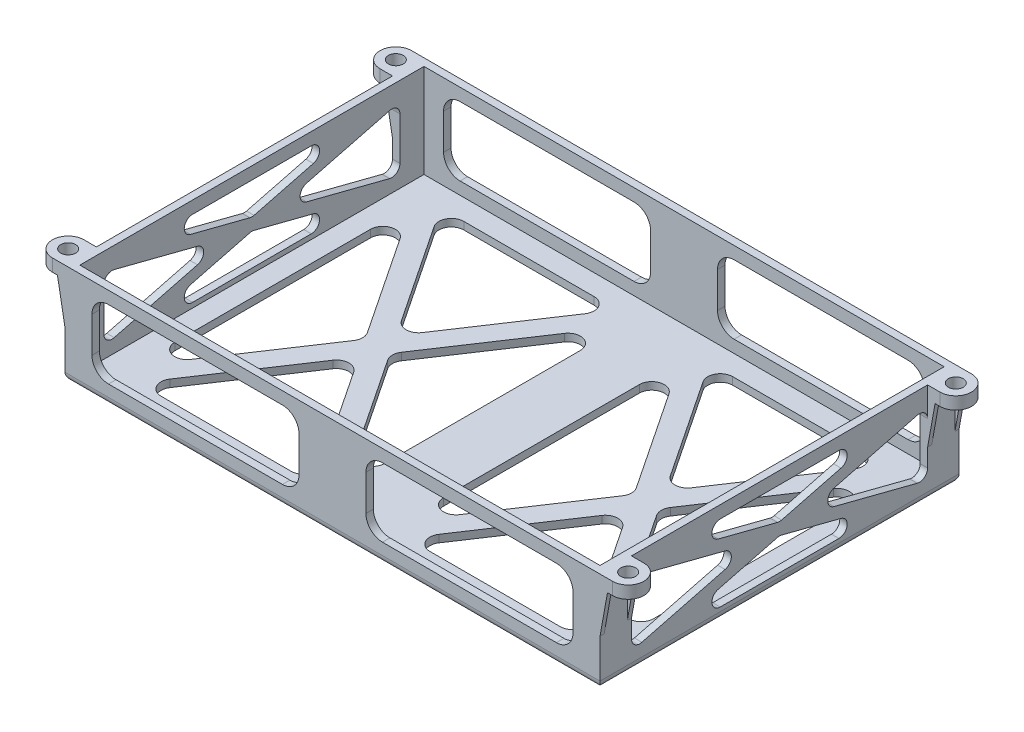
SolidWorks part; units mm, degrees
other "Markup2"
sketch "Sketch32" plane through (-159.4724, 0, 108) normal (-0.262, -0.0774, 0.962) x (0.8638, -0.4632, 0.198)
ref_plane "Front Plane" through (0, 0, 0) normal (0, 0, 1) x (1, 0, 0)
ref_plane "Top Plane" through (0, 0, 0) normal (0, 1, 0) x (1, 0, 0)
ref_plane "Right Plane" through (0, 0, 0) normal (1, 0, 0) x (0, 0, -1)
sketch "Sketch1" plane through (0, 0, 0) normal (0, 1, 0) x (1, 0, 0)
  line L0 (-2.286, -2.286) -> (-2.286, -107.823) construction
  line L1 (0, 0) -> (-164.084, 0)
  line L2 (0, 0) -> (0, -110.109)
  line L3 (0, -110.109) -> (-164.084, -110.109)
  line L4 (-164.084, 0) -> (-164.084, -110.109)
  line L5 (-2.286, -107.823) -> (-161.798, -107.823) construction
  line L6 (-161.798, -2.286) -> (-161.798, -107.823) construction
  line L7 (-2.286, -2.286) -> (-161.798, -2.286) construction
  dimension "D1" = 2.286
  dimension "D2" = 105.537
  dimension "D3" = 159.512
extrude "Boss-Extrude1" add sketch "Sketch1" along normal blind 30.988 contours L1 L4 L3 L2
shell "Shell1" thickness 2.286 removed face at (-82.042, 30.988, 55.0545)
sketch "Sketch7" plane through (0, 30.988, 0) normal (0, 1, 0) x (1, 0, 0)
  line L0 (-167.894, 0) -> (-164.084, 0)
  line L1 (-164.084, 0) -> (-164.084, -9.652)
  line L2 (-164.084, 0) -> (-164.084, -110.109) construction
  line L3 (-164.084, -9.652) -> (-167.894, -9.652)
  line L4 (-82.042, -1000) -> (-82.042, 49000) construction
  line L5 (0, 0) -> (-164.084, 0) construction
  line L6 (-1150, -55.0545) -> (48850, -55.0545) construction
  line L7 (-161.798, -2.286) -> (-161.798, -107.823) construction
  line L8 (-164.084, -100.457) -> (-167.894, -100.457)
  line L9 (-164.084, -110.109) -> (-164.084, -100.457)
  line L10 (-167.894, -110.109) -> (-164.084, -110.109)
  line L11 (3.81, -110.109) -> (0, -110.109)
  line L12 (0, -110.109) -> (0, -100.457)
  line L13 (0, -100.457) -> (3.81, -100.457)
  line L14 (0, -9.652) -> (3.81, -9.652)
  line L15 (0, 0) -> (0, -9.652)
  line L16 (3.81, 0) -> (0, 0)
  circle A0 centre (-167.894, -4.826) radius 2.286
  arc A2 (-167.894, 0) -> (-167.894, -9.652) centre (-167.894, -4.826) ccw
  arc A3 (-167.894, -110.109) -> (-167.894, -100.457) centre (-167.894, -105.283) cw
  circle A4 centre (-167.894, -105.283) radius 2.286
  circle A5 centre (3.81, -105.283) radius 2.286
  arc A6 (3.81, -110.109) -> (3.81, -100.457) centre (3.81, -105.283) ccw
  arc A7 (3.81, 0) -> (3.81, -9.652) centre (3.81, -4.826) cw
  circle A8 centre (3.81, -4.826) radius 2.286
  point P14 (-82.042, 0)
  point P19 (-161.798, -55.0545)
  dimension "D1" = 2.54
  dimension "D3" = 4.572
  dimension "D2" = 3.81
extrude "Boss-Extrude7" add sketch "Sketch7" against normal blind 3.81
ref_plane "Plane1" through (0, 0, 55.0545) normal (0, 0, -1) x (-1, 0, 0)
ref_plane "Plane2" through (-82.042, 0, 0) normal (-1, 0, 0) x (0, 0, 1)
sketch "Sketch33" plane through (0, 0, 0) normal (1, 0, 0) x (0, 0, -1)
  line L0 (-9.652, 27.178) -> (-100.457, 3.81) construction
  line L1 (-9.652, 27.178) -> (-100.457, 27.178)
  line L2 (-9.652, 27.178) -> (-9.652, 3.81)
  line L3 (-9.652, 3.81) -> (-100.457, 3.81)
  line L4 (-100.457, 27.178) -> (-100.457, 3.81)
  line L5 (-9.652, 3.81) -> (-100.457, 27.178) construction
  line L6 (-9.652, 27.178) -> (-9.652, 30.988) construction
  line L7 (-55.0545, 17.3299) -> (-93.3228, 27.178)
  line L8 (-9.652, 30.988) -> (-100.457, 30.988) construction
  line L10 (0, 27.178) -> (-9.652, 27.178) construction
  line L11 (-55.0545, 13.6581) -> (-93.3228, 3.81)
  line L12 (0, 0) -> (-110.109, 0) construction
  line L13 (-9.652, 5.6459) -> (-47.9203, 15.494)
  line L14 (-16.7862, 27.178) -> (-55.0545, 17.3299)
  line L15 (-16.7862, 3.81) -> (-55.0545, 13.6581)
  line L16 (-9.652, 25.3421) -> (-47.9203, 15.494)
  line L17 (-9.2089, 25.4561) -> (-100.0139, 2.0881) construction
  line L18 (-10.0951, 28.8999) -> (-100.9001, 5.5319) construction
  line L19 (-9.2089, 5.5319) -> (-100.0139, 28.8999) construction
  line L20 (-10.0951, 2.0881) -> (-100.9001, 25.4561) construction
  line L21 (-62.1887, 15.494) -> (-100.457, 5.6459)
  line L22 (-62.1887, 15.494) -> (-100.457, 25.3421)
  point P10 (-55.0545, 30.988)
  point P12 (-55.0545, 27.178)
  dimension "D1" = 3.81
  dimension "D2" = 1.778
  dimension "D3" = 1.778
extrude "Cut-Extrude1" cut sketch "Sketch33" against normal up to surface (2.286 mm away) contours L3 L15 L11 | L2 L16 L13 | L21 L22 L4 | L14 L1 L7 region at (0, 23.8953, 55.0545) region at (0, 15.494, 22.4081) region at (0, 15.494, 87.7009) region at (0, 7.0927, 55.0545) up to face at (-2.286, 16.637, 55.0545)
fillet "Fillet1" radius 2.54 12 edges at (-1.143, 3.81, 16.7862) (-1.143, 13.6581, 55.0545) (-1.143, 3.81, 93.3228) (-1.143, 5.6459, 100.457) (-1.143, 25.3421, 100.457) (-1.143, 15.494, 62.1887) (-1.143, 17.3299, 55.0545) (-1.143, 27.178, 93.3228) (-1.143, 27.178, 16.7862) (-1.143, 5.6459, 9.652) (-1.143, 25.3421, 9.652) (-1.143, 15.494, 47.9203)
mirror "Mirror1" about plane through (-82.042, 0, 0) normal (-1, 0, 0) of "Fillet1", "Cut-Extrude1"
sketch "Sketch34" plane through (0, 0, 107.823) normal (0, 0, -1) x (-1, 0, 0)
  line L0 (92.298, 16.637) -> (71.786, 16.637) construction
  line L1 (150.718, 6.096) -> (97.378, 6.096)
  line L2 (155.798, 11.176) -> (155.798, 22.098)
  line L3 (150.718, 27.178) -> (97.378, 27.178)
  line L4 (92.298, 11.176) -> (92.298, 22.098)
  line L5 (66.706, 6.096) -> (13.366, 6.096)
  line L6 (71.786, 11.176) -> (71.786, 22.098)
  line L7 (66.706, 27.178) -> (13.366, 27.178)
  line L8 (8.286, 11.176) -> (8.286, 22.098)
  line L9 (2.286, 30.988) -> (161.798, 30.988) construction
  line L10 (161.798, 30.988) -> (161.798, 2.286) construction
  line L11 (2.286, 2.286) -> (161.798, 2.286) construction
  arc A0 (150.718, 6.096) -> (155.798, 11.176) centre (150.718, 11.176) ccw
  arc A1 (155.798, 22.098) -> (150.718, 27.178) centre (150.718, 22.098) ccw
  arc A2 (97.378, 27.178) -> (92.298, 22.098) centre (97.378, 22.098) ccw
  arc A3 (97.378, 6.096) -> (92.298, 11.176) centre (97.378, 11.176) cw
  arc A4 (13.366, 6.096) -> (8.286, 11.176) centre (13.366, 11.176) cw
  arc A5 (66.706, 6.096) -> (71.786, 11.176) centre (66.706, 11.176) ccw
  arc A6 (71.786, 22.098) -> (66.706, 27.178) centre (66.706, 22.098) ccw
  arc A7 (13.366, 27.178) -> (8.286, 22.098) centre (13.366, 22.098) ccw
  point P12 (82.042, 30.988)
  point P13 (82.042, 16.637)
  point P16 (161.798, 16.637)
  point P17 (155.798, 16.637)
  point P30 (8.286, 6.096)
  point P33 (71.786, 6.096)
  dimension "D4" = 5.08
  dimension "D1" = 6
  dimension "D2" = 63.5
  dimension "D3" = 3.81
extrude "Cut-Extrude2" cut sketch "Sketch34" against normal through all both and the other way through all
fillet "Fillet2" radius 2.54 4 edges at (-82.042, 0, 0) (-164.084, 0, 55.0545) (-82.042, 0, 110.109) (0, 0, 55.0545)
sketch "Sketch36" plane through (0, 2.286, 0) normal (0, 1, 0) x (1, 0, 0)
  line L0 (-103.2935, -8.636) -> (-143.2465, -8.636)
  line L2 (-164.084, 0) -> (-164.084, -110.109) construction
  line L4 (-151.638, -97.663) -> (-94.902, -12.446) construction
  line L6 (-91.092, -85.059) -> (-91.092, -25.05)
  line L7 (-151.638, -12.446) -> (-94.902, -97.663) construction
  line L9 (0, 0) -> (-164.084, 0) construction
  line L11 (-164.084, -110.109) -> (0, -110.109) construction
  line L14 (-155.448, -25.05) -> (-155.448, -85.059)
  line L15 (-143.2465, -101.473) -> (-103.2935, -101.473)
  line L16 (-155.6918, -103.7518) -> (-93.6147, -10.5125) construction
  line L17 (-82.042, -1089.6267) -> (-82.042, 48910.3733) construction
  line L18 (-148.4666, -22.9385) -> (-128.4901, -52.943)
  line L19 (-146.4179, -95.5515) -> (-126.4414, -65.547)
  line L22 (-146.4179, -14.5575) -> (-126.4414, -44.562)
  line L23 (-148.4666, -87.1705) -> (-128.4901, -57.166)
  line L26 (-148.9952, -10.6864) -> (-92.2592, -95.9034) construction
  line L27 (-154.2808, -14.2056) -> (-97.5448, -99.4226) construction
  line L28 (-153.049, -105.5114) -> (-90.9719, -12.272) construction
  line L29 (-158.3347, -101.9923) -> (-96.2575, -8.7529) construction
  line L30 (-2.54, -107.569) -> (-161.544, -107.569) construction
  line L31 (-12.446, -12.446) -> (-69.182, -97.663) construction
  line L32 (-12.446, -97.663) -> (-69.182, -12.446) construction
  line L33 (-43.9854, -44.562) -> (-63.9619, -14.5575)
  line L38 (-118.0499, -52.943) -> (-98.0734, -22.9385)
  line L39 (-118.0499, -57.166) -> (-98.0734, -87.1705)
  line L40 (-120.0986, -65.547) -> (-100.1221, -95.5515)
  line L41 (-120.0986, -44.562) -> (-100.1221, -14.5575)
  line L42 (-43.9854, -65.547) -> (-63.9619, -95.5515)
  line L43 (-46.0341, -57.166) -> (-66.0106, -87.1705)
  line L44 (-46.0341, -52.943) -> (-66.0106, -22.9385)
  line L45 (-15.6174, -87.1705) -> (-35.5939, -57.166)
  line L46 (-17.6661, -14.5575) -> (-37.6426, -44.562)
  line L47 (-17.6661, -95.5515) -> (-37.6426, -65.547)
  line L48 (-15.6174, -22.9385) -> (-35.5939, -52.943)
  line L49 (-20.8375, -101.473) -> (-60.7905, -101.473)
  line L50 (-8.636, -25.05) -> (-8.636, -85.059)
  line L51 (-72.992, -85.059) -> (-72.992, -25.05)
  line L52 (-60.7905, -8.636) -> (-20.8375, -8.636)
  arc A12 (-146.4179, -14.5575) -> (-143.2465, -8.636) centre (-143.2465, -12.446) cw
  arc A13 (-100.1221, -14.5575) -> (-103.2935, -8.636) centre (-103.2935, -12.446) ccw
  arc A14 (-98.0734, -22.9385) -> (-91.092, -25.05) centre (-94.902, -25.05) cw
  arc A15 (-118.0499, -52.943) -> (-118.0499, -57.166) centre (-114.8785, -55.0545) ccw
  arc A16 (-98.0734, -87.1705) -> (-91.092, -85.059) centre (-94.902, -85.059) ccw
  arc A17 (-126.4414, -65.547) -> (-120.0986, -65.547) centre (-123.27, -67.6585) cw
  arc A18 (-100.1221, -95.5515) -> (-103.2935, -101.473) centre (-103.2935, -97.663) cw
  arc A19 (-146.4179, -95.5515) -> (-143.2465, -101.473) centre (-143.2465, -97.663) ccw
  arc A20 (-148.4666, -87.1705) -> (-155.448, -85.059) centre (-151.638, -85.059) cw
  arc A21 (-128.4901, -52.943) -> (-128.4901, -57.166) centre (-131.6615, -55.0545) cw
  arc A22 (-148.4666, -22.9385) -> (-155.448, -25.05) centre (-151.638, -25.05) ccw
  arc A23 (-120.0986, -44.562) -> (-126.4414, -44.562) centre (-123.27, -42.4505) cw
  arc A24 (-43.9854, -44.562) -> (-37.6426, -44.562) centre (-40.814, -42.4505) ccw
  arc A25 (-15.6174, -22.9385) -> (-8.636, -25.05) centre (-12.446, -25.05) cw
  arc A26 (-35.5939, -52.943) -> (-35.5939, -57.166) centre (-32.4225, -55.0545) ccw
  arc A27 (-15.6174, -87.1705) -> (-8.636, -85.059) centre (-12.446, -85.059) ccw
  arc A28 (-17.6661, -95.5515) -> (-20.8375, -101.473) centre (-20.8375, -97.663) cw
  arc A29 (-63.9619, -95.5515) -> (-60.7905, -101.473) centre (-60.7905, -97.663) ccw
  arc A30 (-37.6426, -65.547) -> (-43.9854, -65.547) centre (-40.814, -67.6585) ccw
  arc A31 (-66.0106, -87.1705) -> (-72.992, -85.059) centre (-69.182, -85.059) cw
  arc A32 (-46.0341, -52.943) -> (-46.0341, -57.166) centre (-49.2055, -55.0545) cw
  arc A33 (-66.0106, -22.9385) -> (-72.992, -25.05) centre (-69.182, -25.05) ccw
  arc A34 (-63.9619, -14.5575) -> (-60.7905, -8.636) centre (-60.7905, -12.446) cw
  arc A35 (-17.6661, -14.5575) -> (-20.8375, -8.636) centre (-20.8375, -12.446) ccw
  point P18 (-82.042, -107.569)
  point P87 (-119.4557, -55.0545)
  point P90 (-91.092, -97.6565)
  point P93 (-123.27, -60.7836)
  point P96 (-96.1797, -101.473)
  point P99 (-150.3603, -101.473)
  point P102 (-155.448, -97.6565)
  point P107 (-8.636, -97.6565)
  point P108 (-13.7237, -101.473)
  point P109 (-67.9043, -101.473)
  point P110 (-40.814, -60.7836)
  point P111 (-72.992, -97.6565)
  point P112 (-44.6283, -55.0545)
  dimension "D8" = 3.81
  dimension "D7" = 3.81
  dimension "D2" = 8.636
  dimension "D3" = 3.175
  dimension "D5" = 8.636
  dimension "D6" = 72.992
  dimension "D1" = 8.636
  dimension "D4" = 3.175
extrude "Cut-Extrude3" cut sketch "Sketch36" against normal through all
sketch "Sketch39" plane through (0, 0, 0) normal (0, 0, -1) x (-1, 0, 0)
  line L0 (166.37, 27.178) -> (164.084, 14.478)
  line L1 (164.084, 27.178) -> (164.084, 2.54) construction
  line L3 (164.084, 27.178) -> (167.894, 27.178) construction
  dimension "D1" = 12.7
  dimension "D2" = 2.286
sketch "Sketch40" plane through (0, 0, 9.652) normal (0, 0, 1) x (1, 0, 0)
  line L0 (-166.37, 27.178) -> (-164.084, 14.478) construction
  line L1 (-166.37, 27.178) -> (-164.084, 14.478)
rib "Rib1" sketch "Sketch40" sketch "Sketch40" thickness 1.27 extrusion direction parallel to sketch draft on no parameters "D1"=1.27
rib "Rib2" sketch "Sketch39" sketch "Sketch39" thickness 1.27 extrusion direction parallel to sketch draft on no parameters "D1"=1.27
mirror "Mirror2" about plane through (0, 0, 55.0545) normal (0, 0, -1) of "Rib1", "Rib2"
mirror "Mirror3" about plane through (-82.042, 0, 0) normal (-1, 0, 0) of "Mirror2"
